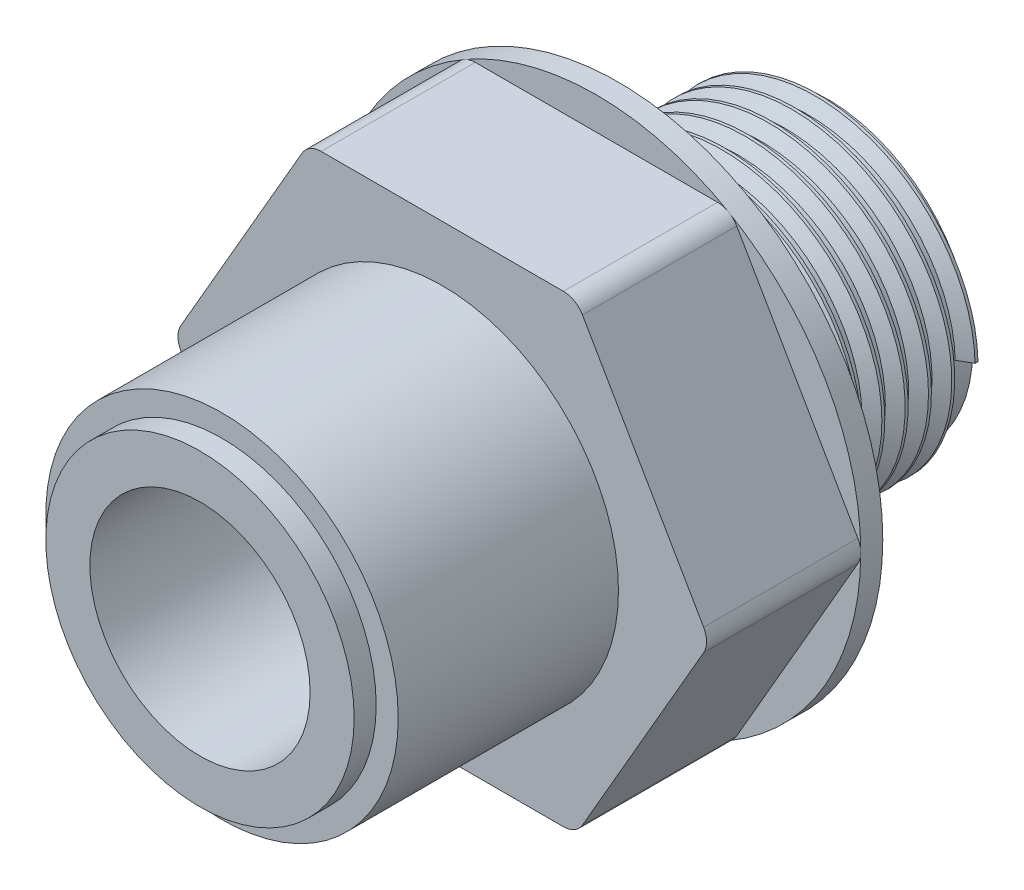
SolidWorks part; units mm, degrees
ref_plane "Front Plane" through (0, 0, 0) normal (0, 0, 1) x (1, 0, 0)
ref_plane "Top Plane" through (0, 0, 0) normal (0, 1, 0) x (1, 0, 0)
ref_plane "Right Plane" through (0, 0, 0) normal (1, 0, 0) x (0, 0, -1)
sketch "Sketch2" plane through (0, 0, 0) normal (1, 0, 0) x (0, 0, -1)
  line L0 (-17.6659, 0) -> (22.2536, 0) construction
  line L1 (0, 3.75) -> (28.5, 3.75)
  line L2 (28.5, 3.75) -> (28.5, 6.58)
  line L3 (28.5, 6.58) -> (19, 6.58)
  line L4 (19, 6.58) -> (19, 12)
  line L5 (19, 12) -> (11, 12)
  line L8 (11, 12) -> (11, 8)
  line L9 (11, 8) -> (0, 8)
  line L10 (0, 8) -> (0, 3.75)
  dimension "D1" = 28.5
  dimension "D2" = 19
  dimension "D3" = 8
  dimension "D4" = 12
  dimension "D5" = 3.75
  dimension "D8" = 6.58
  dimension "D9" = 8
revolve "Revolve1" add sketch "Sketch2" angle 360 about L0
thread "Thread1" pitch 1.0583 method extrude profile "Thread Profile1" start angle 0, offset 0, length 0, pitch 1.0583, diameter 13.16
ref_plane "Plane1" through (6.58, 0, -28.5) normal (0, -1, 0) x (1, 0, 0)
sketch "Thread Profile1" plane through (6.58, 0, -28.5) normal (0, -1, 0) x (1, 0, 0)
  line L0 (0, 0) -> (0, 1.0583) construction
  line L1 (0, 0) -> (0.5728, 0.3307)
  line L2 (0.5728, 0.3307) -> (0.5728, 0.463)
  line L3 (0.5728, 0.463) -> (0, 0.7937)
  line L4 (0.5728, 0.3969) -> (0, 0.3969) construction
  line L11 (0, 0) -> (0, 0.7937)
  point P2 (0, 0)
  dimension "Pitch" = 1.0583
  dimension "Profile_Angle" = 60
  dimension "Profile_Land" = 0.1323
  dimension "Profile_Height" = 0.5728
sketch "Sketch6" plane through (0, 0, 0) normal (0, 0, 1) x (1, 0, 0)
  circle A0 centre (0, 0) radius 7
  circle A1 centre (0, 0) radius 8 construction
  dimension "D1" = 1
extrude "Cut-Extrude1" cut sketch "Sketch6" against normal blind 1 flip side to cut
sketch "Sketch8" plane through (0, 0, -11) normal (0, 0, 1) x (1, 0, 0)
  line L0 (-5.5, 10.5263) -> (5.5, 10.5263)
  line L1 (6.366, 10.0263) -> (11.866, 0.5)
  line L2 (11.866, -0.5) -> (6.366, -10.0263)
  line L3 (5.5, -10.5263) -> (-5.5, -10.5263)
  line L4 (-6.366, -10.0263) -> (-11.866, -0.5)
  line L5 (-11.866, 0.5) -> (-6.366, 10.0263)
  arc A0 (5.5, 10.5263) -> (6.366, 10.0263) centre (5.5, 9.5263) cw
  arc A1 (11.866, 0.5) -> (11.866, -0.5) centre (11, 0) cw
  arc A2 (6.366, -10.0263) -> (5.5, -10.5263) centre (5.5, -9.5263) cw
  arc A3 (-5.5, -10.5263) -> (-6.366, -10.0263) centre (-5.5, -9.5263) cw
  arc A4 (-11.866, -0.5) -> (-11.866, 0.5) centre (-11, 0) cw
  arc A5 (-5.5, 10.5263) -> (-6.366, 10.0263) centre (-5.5, 9.5263) ccw
  circle A6 centre (0, 0) radius 12 construction
  dimension "D1" = 1
extrude "Cut-Extrude3" cut sketch "Sketch8" against normal blind 7 flip side to cut
sketch "Sketch9" plane through (0, 0, 0) normal (0, 0, 1) x (1, 0, 0)
  circle A0 centre (0, 0) radius 5
extrude "Cut-Extrude4" cut sketch "Sketch9" against normal up to surface (19 mm away) up to face at (12, 0, -19)
